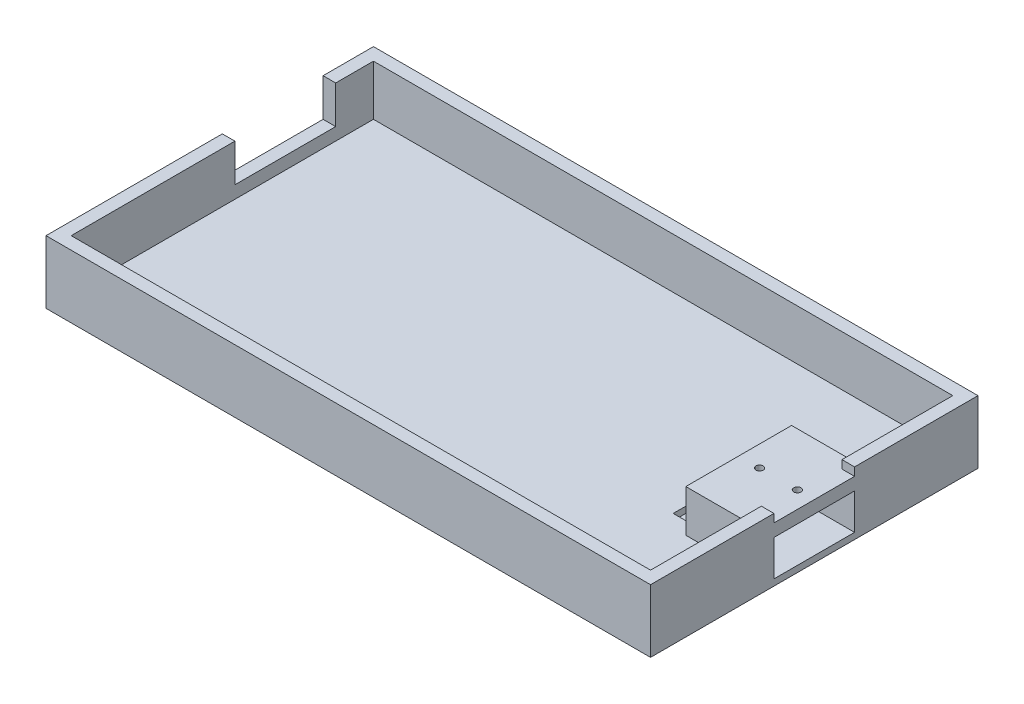
SolidWorks part; units mm, degrees
ref_plane "Front Plane" through (0, 0, 0) normal (0, 0, 1) x (1, 0, 0)
ref_plane "Top Plane" through (0, 0, 0) normal (0, 1, 0) x (1, 0, 0)
ref_plane "Right Plane" through (0, 0, 0) normal (1, 0, 0) x (0, 0, -1)
sketch "Sketch1" plane through (0, 0, 0) normal (0, 1, 0) x (1, 0, 0)
  line L1 (-152.4, -82.55) -> (152.4, -82.55)
  line L2 (-152.4, -82.55) -> (-152.4, 82.55)
  line L3 (-152.4, 82.55) -> (152.4, 82.55)
  line L4 (152.4, -82.55) -> (152.4, 82.55)
  line L5 (-152.4, -82.55) -> (152.4, 82.55) construction
  line L6 (-152.4, 82.55) -> (152.4, -82.55) construction
  point P0 (0, 0)
  dimension "D1" = 304.8
  dimension "D2" = 165.1
extrude "Boss-Extrude1" add sketch "Sketch1" along normal blind 6.35
sketch "Sketch2" plane through (0, 6.35, 0) normal (0, 1, 0) x (1, 0, 0)
  line L0 (152.4, -82.55) -> (152.4, 82.55) construction
  line L1 (-152.4, 82.55) -> (152.4, 82.55)
  line L2 (-152.4, 82.55) -> (-152.4, 76.2)
  line L3 (-152.4, 76.2) -> (152.4, 76.2)
  line L4 (152.4, 82.55) -> (152.4, 76.2)
  line L5 (-152.4, 82.55) -> (-152.4, -82.55) construction
  line L6 (152.4, -82.55) -> (-152.4, -82.55)
  line L7 (152.4, -82.55) -> (152.4, -76.2)
  line L8 (152.4, -76.2) -> (-152.4, -76.2)
  line L9 (-152.4, -82.55) -> (-152.4, -76.2)
  line L11 (-152.4, -76.2) -> (-146.05, -76.2)
  line L12 (-152.4, -76.2) -> (-152.4, 76.2)
  line L13 (-152.4, 76.2) -> (-146.05, 76.2)
  line L14 (-146.05, -76.2) -> (-146.05, 76.2)
  line L15 (152.4, 76.2) -> (146.05, 76.2)
  line L16 (152.4, 76.2) -> (152.4, -76.2)
  line L17 (152.4, -76.2) -> (146.05, -76.2)
  line L18 (146.05, 76.2) -> (146.05, -76.2)
  line M13 (152.4, -82.55) -> (152.4, 82.55)
  line M14 (152.4, 82.55) -> (-152.4, 82.55)
  line M15 (-152.4, 82.55) -> (-152.4, -82.55)
  line M16 (-152.4, -82.55) -> (152.4, -82.55)
  dimension "D1" = 6.35
extrude "Boss-Extrude2" add sketch "Sketch2" along normal blind 25.4 contours L8 L14 L3 M15 | L3 M15 M13 M14 | L3 L18 L8 M13 | L8 M13 M15 M16 region at (0, 6.35, -79.375) region at (-149.225, 6.35, 0) region at (149.225, 6.35, 0) region at (0, 6.35, 79.375)
sketch "Sketch3" plane through (0, 31.75, 0) normal (0, 1, 0) x (1, 0, 0)
  line L0 (146.05, 76.2) -> (146.05, -76.2) construction
  line L1 (146.05, 20.32) -> (152.4, 20.32)
  line L2 (146.05, 20.32) -> (146.05, -20.32)
  line L3 (146.05, -20.32) -> (152.4, -20.32)
  line L4 (152.4, 20.32) -> (152.4, -20.32)
  line L5 (152.4, -82.55) -> (152.4, 82.55) construction
  point P8 (146.05, 0)
  dimension "D1" = 40.64
extrude "Cut-Extrude1" cut sketch "Sketch3" against normal up to surface (25.4 mm away) up to face at (0, 6.35, 0)
sketch "Sketch4" plane through (0, 6.35, 0) normal (0, 1, 0) x (1, 0, 0)
  line L0 (146.05, -20.32) -> (152.4, -20.32) construction
  line L1 (152.4, 20.32) -> (101.6, 20.32)
  line L2 (152.4, 20.32) -> (152.4, -20.32)
  line L3 (152.4, -20.32) -> (101.6, -20.32)
  line L4 (101.6, 20.32) -> (101.6, -20.32)
  dimension "D1" = 50.8
extrude "Cut-Extrude2" cut sketch "Sketch4" against normal blind 3.175
sketch "Sketch5" plane through (0, 6.35, 0) normal (0, 1, 0) x (1, 0, 0)
  line L1 (146.05, 20.32) -> (114.3, 20.32)
  line L2 (146.05, 20.32) -> (146.05, 26.67)
  line L3 (146.05, 26.67) -> (114.3, 26.67)
  line L4 (114.3, 20.32) -> (114.3, 26.67)
  dimension "D1" = 31.75
  dimension "D2" = 6.35
extrude "Boss-Extrude3" add sketch "Sketch5" along normal up to surface (14.913 mm away)
sketch "Sketch6" plane through (0, 21.263, 0) normal (0, 1, 0) x (1, 0, 0)
  line L1 (114.3, 26.67) -> (152.4, 26.67)
  line L2 (114.3, 26.67) -> (114.3, 0)
  line L3 (114.3, 0) -> (152.4, 0)
  line L4 (152.4, 26.67) -> (152.4, 0)
  line L5 (152.4, 20.32) -> (152.4, 82.55) construction
extrude "Boss-Extrude4" add sketch "Sketch6" along normal blind 6.35
mirror "Mirror1" about plane through (0, 0, 0) normal (0, 0, 1) of "Boss-Extrude4", "Boss-Extrude3"
sketch "Sketch7" plane through (0, 27.613, 0) normal (0, 1, 0) x (1, 0, 0)
  circle A0 centre (124.8, 0) radius 1.85 construction
  circle A1 centre (143.9, 0) radius 1.85 construction
  circle A2 centre (124.8, 0) radius 1.85
  circle A3 centre (143.9, 0) radius 1.85
extrude "Cut-Extrude3" cut sketch "Sketch7" against normal up to next
sketch "Sketch8" plane through (0, 31.75, 0) normal (0, 1, 0) x (1, 0, 0)
  line L0 (-152.4, 82.55) -> (-152.4, -82.55) construction
  line L1 (-152.4, 57.15) -> (-146.05, 57.15)
  line L2 (-152.4, 57.15) -> (-152.4, 6.35)
  line L3 (-152.4, 6.35) -> (-146.05, 6.35)
  line L4 (-146.05, 57.15) -> (-146.05, 6.35)
  line L5 (-146.05, -76.2) -> (-146.05, 76.2) construction
  line L6 (152.4, 82.55) -> (-152.4, 82.55) construction
  dimension "D1" = 50.8
  dimension "D2" = 25.4
extrude "Cut-Extrude4" cut sketch "Sketch8" against normal blind 19.05
